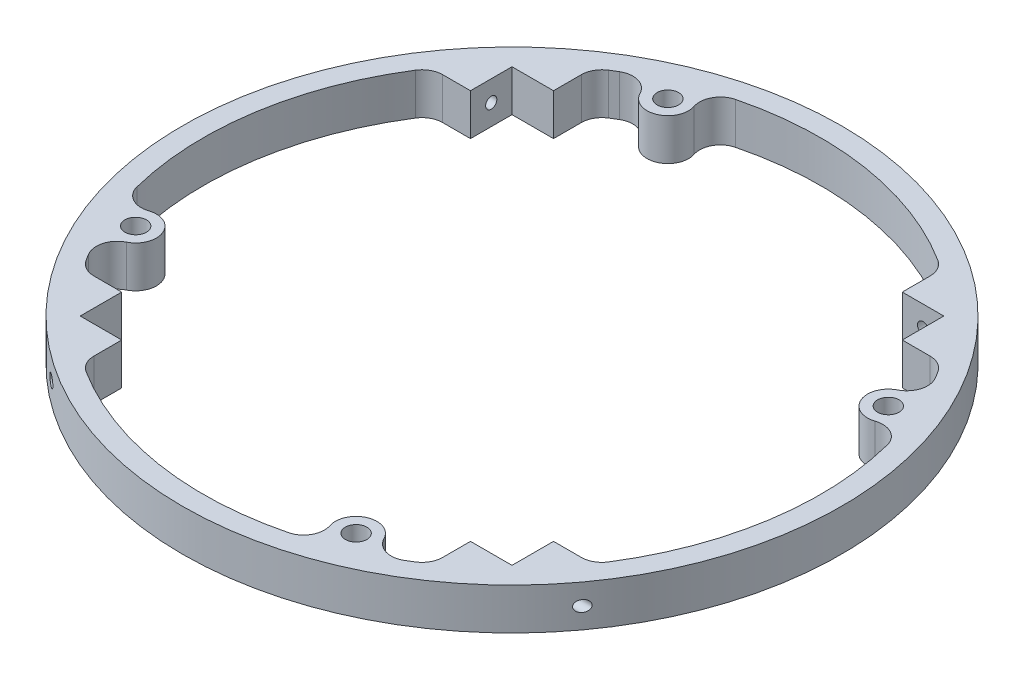
SolidWorks part; units mm, degrees
ref_plane "Front Plane" through (0, 0, 0) normal (0, 0, 1) x (1, 0, 0)
ref_plane "Top Plane" through (0, 0, 0) normal (0, 1, 0) x (1, 0, 0)
ref_plane "Right Plane" through (0, 0, 0) normal (1, 0, 0) x (0, 0, -1)
sketch "Sketch1" plane through (0, 0, 0) normal (0, 1, 0) x (1, 0, 0)
  line L0 (0, 0) -> (0, 84.2831) construction
  line L1 (-52, 52) -> (52, 52) construction
  line L2 (-52, 52) -> (-52, -52) construction
  line L3 (-52, -52) -> (52, -52) construction
  line L4 (52, 52) -> (52, -52) construction
  line L5 (0, 0) -> (-99.9306, 0) construction
  line L6 (0, 0) -> (-52, 52) construction
  line L7 (0, 0) -> (-31.8699, 76.9407) construction
  line L8 (-42, 52) -> (-52, 52)
  line L9 (-52, 52) -> (-52, 42)
  line L10 (-52, 42) -> (-61.3811, 42)
  line L11 (-42, 52) -> (-42, 61.3811)
  line L12 (-33.0171, 66.6447) -> (-31.1681, 62.1807)
  line L13 (-23.7783, 70.4715) -> (-21.9293, 66.0076)
  line L14 (42, 52) -> (42, 61.3811)
  line L15 (52, 52) -> (42, 52)
  line L16 (52, 42) -> (52, 52)
  line L17 (52, 42) -> (61.3811, 42)
  line L18 (66.6447, 33.0171) -> (62.1807, 31.1681)
  line L19 (70.4715, 23.7783) -> (66.0076, 21.9293)
  line L20 (52, -42) -> (61.3811, -42)
  line L21 (52, -52) -> (52, -42)
  line L22 (42, -52) -> (52, -52)
  line L23 (42, -52) -> (42, -61.3811)
  line L24 (33.0171, -66.6447) -> (31.1681, -62.1807)
  line L25 (23.7783, -70.4715) -> (21.9293, -66.0076)
  line L26 (-42, -52) -> (-42, -61.3811)
  line L27 (-52, -52) -> (-42, -52)
  line L28 (-52, -42) -> (-52, -52)
  line L29 (-52, -42) -> (-61.3811, -42)
  line L30 (-66.6447, -33.0171) -> (-62.1807, -31.1681)
  line L31 (-70.4715, -23.7783) -> (-66.0076, -21.9293)
  circle A0 centre (0, 0) radius 79.375
  arc A1 (-61.3811, 42) -> (-74.375, 0) centre (0, 0) ccw
  arc A2 (-42, 61.3811) -> (-33.0171, 66.6447) centre (0, 0) cw
  arc A3 (-31.1681, 62.1807) -> (-21.9293, 66.0076) centre (-26.5487, 64.0941) ccw
  arc A4 (0, 74.375) -> (-23.7783, 70.4715) centre (0, 0) ccw
  arc A5 (42, 61.3811) -> (0, 74.375) centre (0, 0) ccw
  arc A6 (61.3811, 42) -> (66.6447, 33.0171) centre (0, 0) cw
  arc A7 (62.1807, 31.1681) -> (66.0076, 21.9293) centre (64.0941, 26.5487) ccw
  arc A8 (74.375, 0) -> (70.4715, 23.7783) centre (0, 0) ccw
  arc A9 (61.3811, -42) -> (74.375, 0) centre (0, 0) ccw
  arc A10 (42, -61.3811) -> (33.0171, -66.6447) centre (0, 0) cw
  arc A11 (31.1681, -62.1807) -> (21.9293, -66.0076) centre (26.5487, -64.0941) ccw
  arc A12 (0, -74.375) -> (23.7783, -70.4715) centre (0, 0) ccw
  arc A13 (-42, -61.3811) -> (0, -74.375) centre (0, 0) ccw
  arc A14 (-61.3811, -42) -> (-66.6447, -33.0171) centre (0, 0) cw
  arc A15 (-62.1807, -31.1681) -> (-66.0076, -21.9293) centre (-64.0941, -26.5487) ccw
  arc A16 (-74.375, 0) -> (-70.4715, -23.7783) centre (0, 0) ccw
  point P21 (-22.8538, 68.2395)
  point P61 (0, 0)
  dimension "D1" = 158.75
  dimension "D2" = 104
  dimension "D3" = 22.5
  dimension "D4" = 5
  dimension "D5" = 69.375
  dimension "D6" = 10
  dimension "D7" = 10
  dimension "D8" = 4
extrude "Boss-Extrude1" add sketch "Sketch1" along normal blind 10
fillet "Fillet1" radius 5 16 edges at (-70.4715, 5, 23.7783) (-66.6447, 5, 33.0171) (-42, 5, 61.3811) (-61.3811, 5, 42) (23.7783, 5, 70.4715) (33.0171, 5, 66.6447) (42, 5, 61.3811) (61.3811, 5, 42) (70.4715, 5, -23.7783) (66.6447, 5, -33.0171) (61.3811, 5, -42) (42, 5, -61.3811) (-33.0171, 5, -66.6447) (-23.7783, 5, -70.4715) (-42, 5, -61.3811) (-61.3811, 5, -42)
hole_wizard "#6 (0.204) Diameter Hole1" positions "Sketch4" profile "Sketch3" hole size "#6" standard "ANSI Inch" end condition through all
sketch "Sketch4" plane through (0, 10, 0) normal (0, 1, 0) x (1, 0, 0)
  point P0 (64.0941, 26.5487)
sketch "Sketch3" plane through (64.0941, 10, -26.5487) normal (1, 0, 0) x (0, 0, 1)
  line L0 (0, 0) -> (0, 10)
  line L1 (0, 10) -> (2.5908, 10)
  line L2 (2.5908, 10) -> (2.5908, 0)
  line L5 (2.5908, 0) -> (0, 0)
  line L11 (0, -6.35) -> (0, 107.95) construction
  dimension "Thru Hole Dia." = 5.1816
  dimension "Thru Hole Depth" = 10
hole_wizard "#6-32 Tapped Hole2" positions "Sketch8" profile "Sketch9" tap size "#6-32" standard "ANSI Inch" end condition through all
sketch "Sketch8" plane through (0, 0, -52) normal (0, 0, 1) x (1, 0, 0)
  line L0 (52, 0) -> (42, 10)
  point P0 (47, 5)
  point P10 (47, 5)
sketch "Sketch9" plane through (47, 5, -52) normal (1, 0, 0) x (0, -1, 0)
  line L0 (0, 0) -> (0, 27.375)
  line L1 (0, 27.375) -> (1.3525, 27.375)
  line L2 (1.3525, 27.375) -> (1.3525, 0)
  line L5 (1.3525, 0) -> (0, 0)
  line L11 (0, -6.35) -> (0, 107.95) construction
  dimension "Thru Tap Drill Dia." = 2.7051
  dimension "Thru Tap Drill Depth" = 27.375
cosmetic thread "Hole Thread2" parameters "D2"=3.5052
ref_axis "Axis1" through (0, 10.5, 0) along (0, -1, 0)
pattern_circular "CirPattern1" count 4 over 360 about axis through (0, 10.5, 0) along (0, -1, 0) of "#6 (0.204) Diameter Hole1", "#6-32 Tapped Hole2"
equation "\"TubeDiameter\" = 6.250in"
equation "\"D1@Sketch1\"=\"TubeDiameter\""
equation "\"D5@Sketch1\"=\"TubeDiameter\"/2-10mm"
